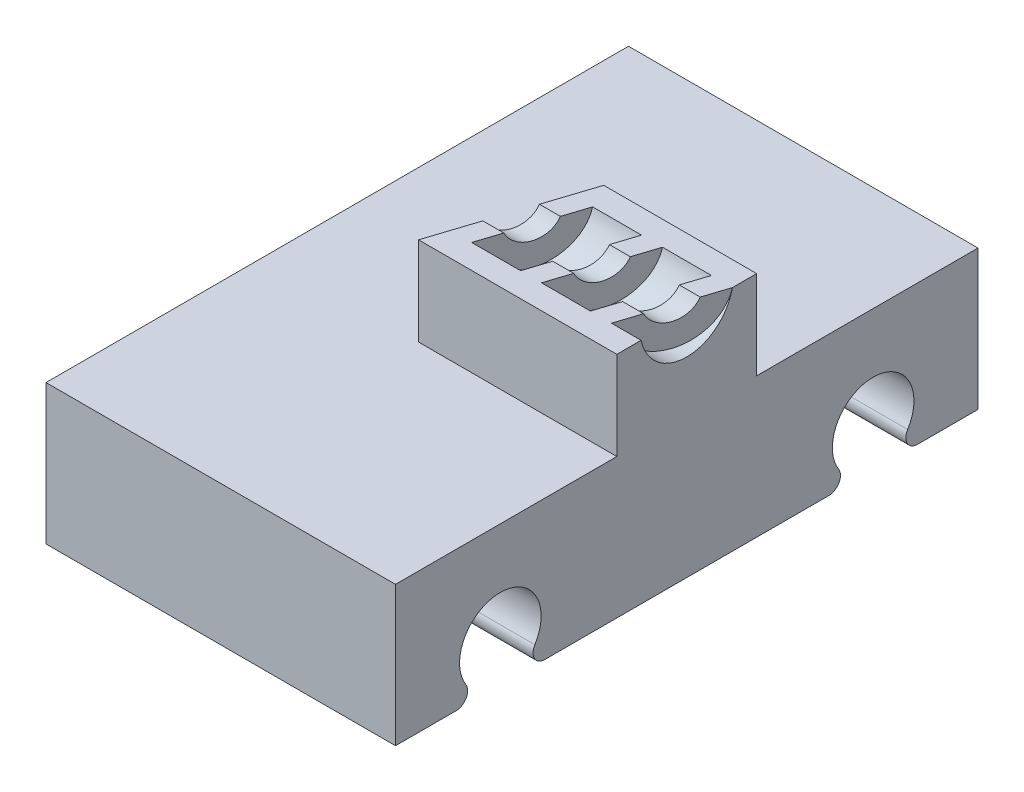
SolidWorks part; units mm, degrees
ref_plane "前视基准面" through (0, 0, 0) normal (0, 0, 1) x (1, 0, 0)
ref_plane "上视基准面" through (0, 0, 0) normal (0, 1, 0) x (1, 0, 0)
ref_plane "右视基准面" through (0, 0, 0) normal (1, 0, 0) x (0, 0, -1)
sketch "草图1" plane through (0, 0, 0) normal (0, 1, 0) x (1, 0, 0)
  line L1 (0, 0) -> (15, 0)
  line L2 (0, 0) -> (0, -25)
  line L3 (0, -25) -> (15, -25)
  line L4 (15, 0) -> (15, -25)
  dimension "D1" = 25
  dimension "D2" = 15
extrude "凸台-拉伸1" add sketch "草图1" along normal blind 6
sketch "草图3" plane through (15, 0, 0) normal (1, 0, 0) x (0, 0, -1)
  line L0 (-12.5, 0) -> (-12.5, 2.3068) construction
  line L1 (-25, 0) -> (0, 0) construction
  circle A0 centre (-20.5, 1.7) radius 1.75
  circle A1 centre (-4.5, 1.7) radius 1.75
  dimension "D1" = 1.7
  dimension "D2" = 3.5
  dimension "D3" = 8
extrude "切除-拉伸1" cut sketch "草图3" against normal up to surface (15 mm away) up to face at (0, 3, 12.5)
fillet "圆角1" radius 0.5 4 edges at (7.5, 0, 4.0847) (7.5, 0, 4.9153) (7.5, 0, 20.0847) (7.5, 0, 20.9153)
sketch "草图4" plane through (0, 6, 0) normal (0, 1, 0) x (1, 0, 0)
  line L0 (0, -12.5) -> (15, -12.5) construction
  line L1 (0, 0) -> (0, -25) construction
  line L2 (15, -25) -> (15, 0) construction
  line L3 (0, -9.5) -> (15, -9.5)
  line L4 (0, -15.5) -> (15, -15.5)
  line L5 (15, -15.5) -> (15, -9.5)
  line L6 (0, -15.5) -> (0, -9.5)
  dimension "D1" = 3
extrude "凸台-拉伸3" add sketch "草图4" along normal blind 2.2
sketch "草图6" plane through (15, 0, 0) normal (1, 0, 0) x (0, 0, -1)
  line L0 (-12.5, 8.2) -> (-12.5, 11.2265) construction
  line L1 (-15.5, 8.2) -> (-9.5, 8.2) construction
  line L2 (-15.5, 8.2) -> (-15.5, 9.8)
  line L3 (-15.5, 9.8) -> (-9.5, 9.8)
  line L4 (-9.5, 9.8) -> (-9.5, 8.2)
  circle A0 centre (-12.5, 10.2) radius 2
  line M9 (-9.5, 8.2) -> (-15.5, 8.2)
  dimension "D1" = 4
  dimension "D2" = 1.6
extrude "凸台-拉伸4" add sketch "草图6" against normal up to surface (15 mm away) contours A0 L4 L3 M9 | A0 L3 L2 M9 region at (15, 8.8744, 14.6698) region at (15, 8.8744, 10.3302) up to face at (0, 3.0209, 12.5)
sketch "草图7" plane through (0, 9.8, 0) normal (0, 1, 0) x (1, 0, 0)
  line L0 (14.1, -10.5404) -> (15, -10.5404)
  line L1 (0, -10.5404) -> (15, -10.5404) construction
  line L2 (12.8266, -14.4596) -> (13.7266, -14.4596)
  line L3 (0, -14.4596) -> (15, -14.4596) construction
  line L4 (14.1, -10.5404) -> (12.8266, -14.4596)
  line L5 (15, -10.5404) -> (13.7266, -14.4596)
  line L6 (11.1, -10.5404) -> (12, -10.5404)
  line L7 (9.8266, -14.4596) -> (10.7266, -14.4596)
  line L8 (11.1, -10.5404) -> (9.8266, -14.4596)
  line L9 (12, -10.5404) -> (10.7266, -14.4596)
  line L10 (8.1, -10.5404) -> (9, -10.5404)
  line L11 (6.8266, -14.4596) -> (7.7266, -14.4596)
  line L12 (8.1, -10.5404) -> (6.8266, -14.4596)
  line L13 (9, -10.5404) -> (7.7266, -14.4596)
  line L14 (5.1, -10.5404) -> (6, -10.5404)
  line L15 (3.8266, -14.4596) -> (4.7266, -14.4596)
  line L16 (5.1, -10.5404) -> (3.8266, -14.4596)
  line L17 (6, -10.5404) -> (4.7266, -14.4596)
  line L18 (2.1, -10.5404) -> (3, -10.5404)
  line L19 (0.8266, -14.4596) -> (1.7266, -14.4596)
  line L20 (2.1, -10.5404) -> (0.8266, -14.4596)
  line L21 (3, -10.5404) -> (1.7266, -14.4596)
  dimension "D3" = 72
  dimension "D1" = 0.9
  dimension "D2" = 0.9
  dimension "D4" = 5
extrude "凸台-拉伸5" add sketch "草图7" against normal up to surface up to face at (7.5, 9, 12.5)
sketch "草图8" plane through (15, 0, 0) normal (1, 0, 0) x (0, 0, -1)
  line L0 (-12.5, 8.2) -> (-12.5, 10.2) construction
  circle A0 centre (-12.5, 10.2) radius 1
  arc A1 (-14.4596, 9.8) -> (-10.5404, 9.8) centre (-12.5, 10.2) ccw construction
  dimension "D1" = 2
extrude "切除-拉伸2" cut sketch "草图8" against normal up to surface (15 mm away) up to face at (0, 3.863, 12.5)
sketch "草图9" plane through (0, 0, 0) normal (-1, 0, 0) x (0, 0, 1)
  line L1 (9.5, 6) -> (15.5, 6)
  line L2 (9.5, 6) -> (9.5, 9.8)
  line L3 (9.5, 9.8) -> (15.5, 9.8)
  line L4 (15.5, 6) -> (15.5, 9.8)
extrude "切除-拉伸3" cut sketch "草图9" against normal up to surface (8.438 mm away) up to face at (7.4633, 9.25, 12.5)
sketch "草图10" plane through (0, 0, 0) normal (0, -1, 0) x (1, 0, 0)
  line L0 (7.5, 25) -> (7.5, 0) construction
  line L1 (0, 25) -> (15, 25) construction
  line L2 (15, 0) -> (0, 0) construction
  line L3 (7.5, 6.4033) -> (7.5, 2.5967) construction
  line L4 (0, 6.4033) -> (15, 6.4033) construction
  line L5 (15, 2.5967) -> (0, 2.5967) construction
  line L6 (7.5, 12.5) -> (9.645, 12.5) construction
  line L7 (3.5, 6.4033) -> (11.5, 6.4033)
  line L8 (3.5, 6.4033) -> (3.5, 2.5967)
  line L9 (3.5, 2.5967) -> (11.5, 2.5967)
  line L10 (11.5, 6.4033) -> (11.5, 2.5967)
  line L11 (3.5, 6.4033) -> (11.5, 2.5967) construction
  line L12 (3.5, 2.5967) -> (11.5, 6.4033) construction
  line L13 (3.5, 22.4033) -> (11.5, 18.5967) construction
  line L14 (3.5, 18.5967) -> (11.5, 22.4033) construction
  line L15 (7.5, 18.5967) -> (7.5, 22.4033) construction
  line L16 (11.5, 18.5967) -> (11.5, 22.4033)
  line L17 (3.5, 22.4033) -> (11.5, 22.4033)
  line L18 (3.5, 18.5967) -> (3.5, 22.4033)
  line L19 (3.5, 18.5967) -> (11.5, 18.5967)
  point P12 (7.5, 4.5)
  point P25 (7.5, 20.5)
  line M6 (0, 6.4033) -> (15, 6.4033)
  line M8 (15, 18.5967) -> (0, 18.5967)
  dimension "D1" = 8
extrude "切除-拉伸5" cut sketch "草图10" against normal blind 5 contours L18 L16 L17 M8 | L10 L8 L9 M6 region at (7.5, 0, 4.5) region at (7.5, 0, 20.5)
sketch "草图12" plane through (0, 0, 0) normal (0, -1, 0) x (1, 0, 0)
  line L0 (15, 6.4033) -> (0, 18.5967) construction
  line L1 (7.5, 12.5) -> (7.5, 11.1011) construction
  line L2 (7.5, 12.5) -> (6.0545, 12.5) construction
  line L3 (15, 12.5) -> (7.5, 6.4033) construction
  line L4 (15, 18.5967) -> (15, 6.4033) construction
  line L5 (3.5, 6.4033) -> (11.5, 6.4033) construction
  line L6 (7.5, 12.5) -> (5.7374, 10.3317) construction
  line L8 (3.75, 15.5484) -> (11.25, 15.5484) construction
  line L11 (11.25, 15.5484) -> (11.25, 9.4516) construction
  line L12 (3.75, 15.5484) -> (11.25, 9.4516) construction
  line L13 (3.75, 9.4516) -> (11.25, 15.5484) construction
  circle A0 centre (11.25, 9.4516) radius 0.9
  circle A1 centre (3.75, 15.5484) radius 0.9
  dimension "D1" = 1.8
  dimension "D2" = 6.0967
  dimension "D3" = 7.5
extrude "切除-拉伸7" cut sketch "草图12" against normal blind 4
equation "\"m\"= 2"
